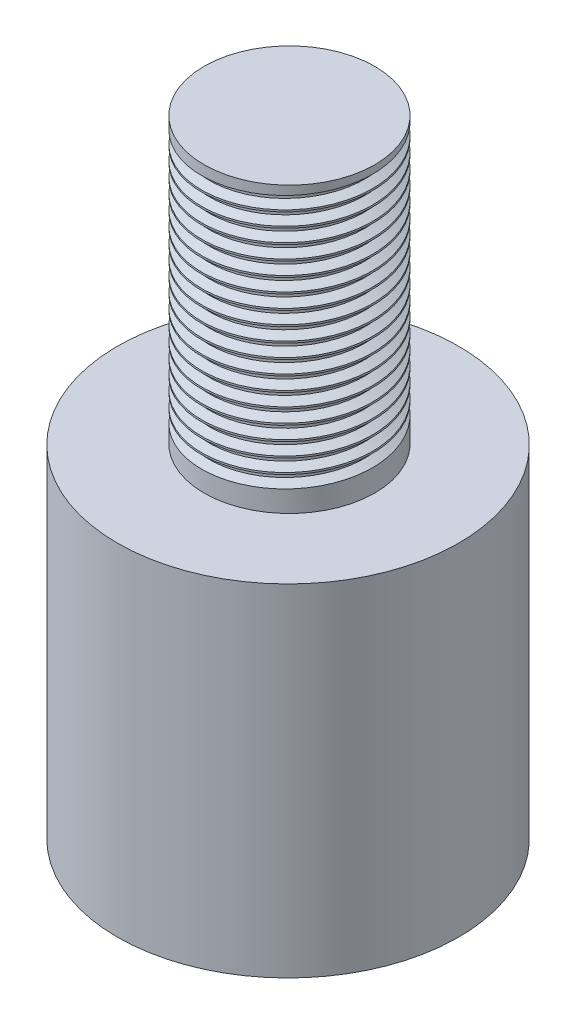
SolidWorks part; units mm, degrees
ref_plane "Front Plane" through (0, 0, 0) normal (0, 0, 1) x (1, 0, 0)
ref_plane "Top Plane" through (0, 0, 0) normal (0, 1, 0) x (1, 0, 0)
ref_plane "Right Plane" through (0, 0, 0) normal (1, 0, 0) x (0, 0, -1)
sketch "Sketch1" plane through (0, 0, 0) normal (0, 1, 0) x (1, 0, 0)
  circle A0 centre (0, 0) radius 3
  dimension "D1" = 6
extrude "Boss-Extrude1" add sketch "Sketch1" along normal blind 6
sketch "Sketch2" plane through (0, 6, 0) normal (0, 1, 0) x (1, 0, 0)
  circle A0 centre (0, 0.0241) radius 1.5
  dimension "D1" = 3
extrude "Boss-Extrude2" add sketch "Sketch2" along normal blind 5
sketch "Sketch3" plane through (0, 0, 0) normal (0, -1, 0) x (-1, 0, 0)
  circle A0 centre (0, 0) radius 1.5
  dimension "D1" = 3
extrude "Cut-Extrude1" cut sketch "Sketch3" against normal blind 3
sketch "Sketch4" plane through (0, 0, 0) normal (0, -1, 0) x (-1, 0, 0)
  circle A0 centre (0, 0) radius 2
  dimension "D1" = 4
extrude "Cut-Extrude2" cut sketch "Sketch4" against normal blind 0.25
thread "Thread1" pitch 0.25 method cut profile "Thread Profile1" start angle 0, offset 0, length 4.5, pitch 0.25, diameter 3
ref_plane "Plane1" through (-1.5, 11, -0.0241) normal (0, 0, 1) x (-1, 0, 0)
sketch "Thread Profile1" plane through (-1.5, 11, -0.0241) normal (0, 0, 1) x (-1, 0, 0)
  line L0 (0, 0) -> (0, 0.25) construction
  line L11 (0, 0) -> (0, 0.2187)
  line L12 (0, 0.2187) -> (-0.1353, 0.1406)
  line L13 (-0.1353, 0.1406) -> (-0.1353, 0.0781)
  line L15 (-0.1353, 0.0781) -> (0, 0)
  line L17 (-0.1353, 0.1094) -> (0, 0.1094) construction
  point P2 (0, 0)
  dimension "Pitch" = 0.25
  dimension "Profile_Angle" = 60
  dimension "Profile_Land" = 0.0625
  dimension "Profile_Height" = 0.1353
